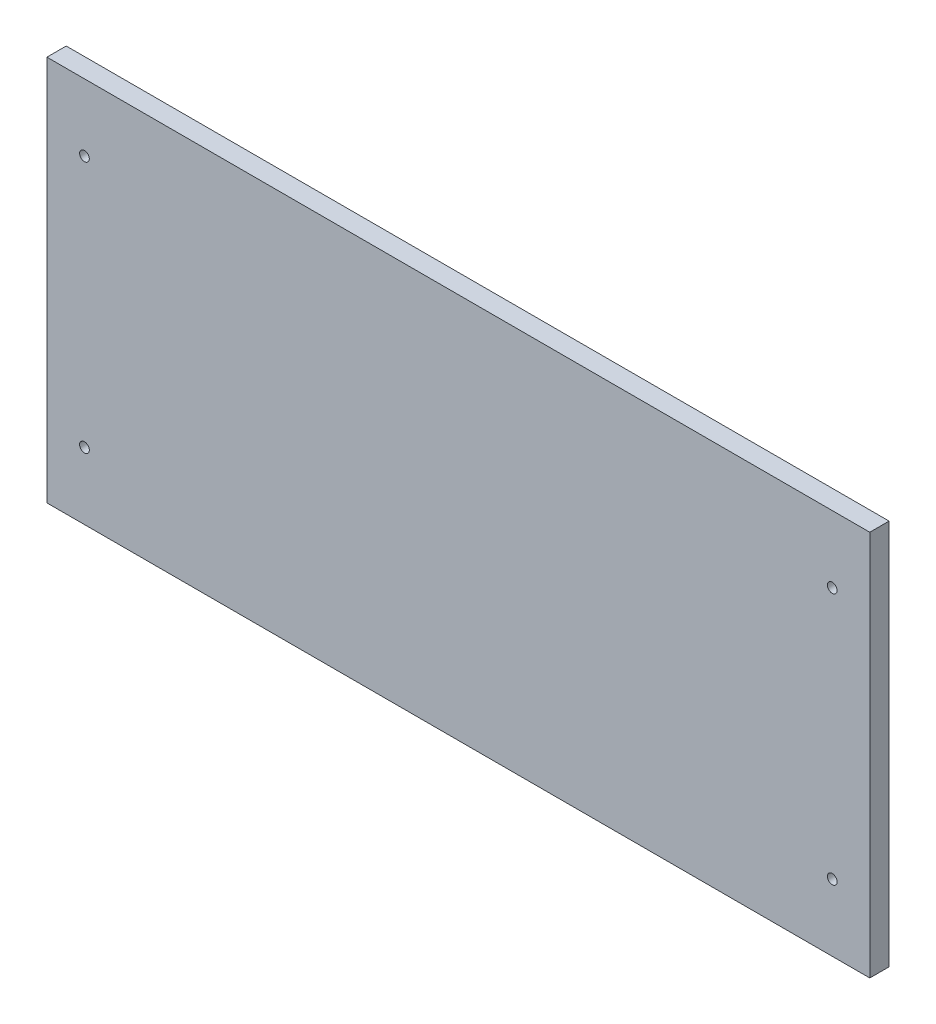
SolidWorks part; units mm, degrees
ref_plane "Front Plane" through (0, 0, 0) normal (0, 0, 1) x (1, 0, 0)
ref_plane "Top Plane" through (0, 0, 0) normal (0, 1, 0) x (1, 0, 0)
ref_plane "Right Plane" through (0, 0, 0) normal (1, 0, 0) x (0, 0, -1)
sketch "Sketch1" plane through (0, 0, 0) normal (0, 0, 1) x (1, 0, 0)
  line L0 (135.35, 127) -> (135.35, 0) construction
  line L1 (0, 0) -> (270.7, 0)
  line L2 (0, 0) -> (0, 127)
  line L3 (0, 127) -> (270.7, 127)
  line L4 (270.7, 0) -> (270.7, 127)
  line L5 (0, 63.5) -> (270.7, 63.5) construction
  circle A3 centre (12.35, 105) radius 1.6
  circle A7 centre (258.35, 105) radius 1.6
  circle A8 centre (258.35, 22) radius 1.6
  circle A9 centre (12.35, 22) radius 1.6
  dimension "D11" = 3.2
  dimension "D1" = 127
  dimension "D2" = 270.7
  dimension "D12" = 12.35
  dimension "D13" = 22
extrude "Wall" add sketch "Sketch1" along normal blind 6.35
sketch "Sketch2" plane through (0, 0, 6.35) normal (0, 0, 1) x (1, 0, 0)
  line L0 (135.35, 127) -> (135.35, 98.425) construction
  line L1 (270.7, 127) -> (0, 127) construction
  line L2 (135.35, 98.425) -> (66.6667, 98.425) construction
  line L3 (135.35, 98.425) -> (204.0333, 98.425) construction
  line L4 (0, 127) -> (0, 0) construction
  circle A0 centre (135.35, 98.425) radius 3.9687
  circle A1 centre (66.6667, 98.425) radius 3.9688
  circle A2 centre (204.0333, 98.425) radius 3.9687
  dimension "D2" = 7.9375
  dimension "D1" = 28.575
  dimension "D3" = 66.6667
extrude "RodSupportCutouts" [suppressed] cut sketch "Sketch2" against normal up to next
sketch "Sketch3" plane through (0, 0, 6.35) normal (0, 0, 1) x (1, 0, 0)
  line L1 (25.4, 88.9) -> (245.3, 88.9)
  line L2 (25.4, 88.9) -> (25.4, 114.3)
  line L3 (25.4, 114.3) -> (245.3, 114.3)
  line L4 (245.3, 88.9) -> (245.3, 114.3)
  line L5 (25.4, 88.9) -> (245.3, 114.3) construction
  line L6 (25.4, 114.3) -> (245.3, 88.9) construction
  line L7 (270.7, 127) -> (0, 127) construction
  line L8 (0, 127) -> (0, 0) construction
  point P0 (135.35, 101.6)
  point P9 (135.35, 127)
  dimension "D1" = 25.4
  dimension "D2" = 25.4
  dimension "D3" = 25.4
extrude "CannulaLargeCutout" [suppressed] cut sketch "Sketch3" against normal up to next
sketch "Sketch4" [suppressed] plane through (0, 0, 9.525) normal (0, 0, 1) x (1, 0, 0)
  line L0 (6, 103.5) -> (194, 103.5) construction
  line L1 (6, 105) -> (6, 22) construction
  line L2 (194, 105) -> (194, 22) construction
  line L3 (200, 127) -> (0, 127) construction
  line L4 (0, 127) -> (0, 0) construction
  circle A0 centre (60, 103.5) radius 6.35
  circle A1 centre (20, 103.5) radius 6.35
  circle A2 centre (100, 103.5) radius 6.35
  circle A3 centre (140, 103.5) radius 6.35
  circle A4 centre (60, 63.5) radius 6.35
  circle A5 centre (100, 63.5) radius 6.35
  circle A6 centre (140, 63.5) radius 6.35
  circle A7 centre (60, 23.5) radius 6.35
  circle A8 centre (100, 23.5) radius 6.35
  circle A9 centre (140, 23.5) radius 6.35
  circle A10 centre (20, 63.5) radius 6.35
  circle A11 centre (20, 23.5) radius 6.35
  circle A12 centre (180, 103.5) radius 6.35
  circle A13 centre (180, 63.5) radius 6.35
  circle A14 centre (180, 23.5) radius 6.35
  point P42 (100, 127)
  point P45 (0, 63.5)
  dimension "D3" = 12.7
  dimension "D1" = 5
  dimension "D2" = 3
extrude "CannulaHoles" [suppressed] cut sketch "Sketch4" against normal up to next
ref_plane "LeftBoundary" through (25.4, 0, 0) normal (-1, 0, 0) x (0, 0, 1)
ref_plane "RightBoundary" through (245.3, 0, 0) normal (1, 0, 0) x (0, 0, -1)
ref_plane "TopBoundary" through (0, 101.6, 0) normal (0, 1, 0) x (1, 0, 0)
ref_plane "BottomBoundary" through (0, 25.4, 0) normal (0, -1, 0) x (-1, 0, 0)
sketch "Sketch5" plane through (0, 0, 6.35) normal (0, 0, 1) x (1, 0, 0)
  line L4 (25.4, 3.4925) -> (25.4, -3.4925) construction
  line L5 (3.4925, 101.6) -> (-3.4925, 101.6) construction
  circle A0 centre (25.4, 101.6) radius 3.9687
  dimension "D1" = 7.9375
extrude "RodSupportCutout" [suppressed] cut sketch "Sketch5" against normal up to next
pattern_linear "SupportPattern" [suppressed] count 7 spacing 36.65 count 5 spacing 19.05 of bodies 105
equation "\"Length\"= 283mm"
equation "\"Width\"= 225mm"
equation "\"WallThickness\"= 0.25in"
equation "\"UpperWaterJacketThickness\"= 28mm"
equation "\"SpacerHeight\"= 80.2mm"
equation "\"SpacerCornerWidth\"= 10mm"
equation "\"SpacerCornerHeight\"= 60.16mm"
equation "\"SpacerPegDiameter\"= 10mm"
equation "\"SpacerPegHeight\"= 10mm"
equation "\"TubingShort\"= 110mm"
equation "\"TubingLong\"= 175mm"
equation "\"PlateLength\"= 252mm"
equation "\"PlateWidth\"= 190mm"
equation "\"PlateHoleDiameter\"= 5.9mm"
equation "\"PlateHoleBottom\"= 2mm"
equation "\"PlateHoleSide\"= 1.55mm"
equation "\"PlateHoleSpacing\"= 3.1mm"
equation "\"PlateThickness\"= 1.55mm"
equation "\"ReservoirBottom\"= 12.5mm"
equation "\"ReservoirSupportWidth\"= 12mm"
equation "\"ReservoirSupportHeight\"= 15.1mm"
equation "\"ReservoirSupportPlacementHeight\"= 50mm"
equation "\"ReservoirHoleDiameter\"= 12.7mm"
equation "\"ReservoirHoleRight\"= 25mm"
equation "\"ReservoirHoleTop\"= \"ReservoirSupportPlacementHeight\""
equation "\"ReservoirHeight\"= 90mm"
equation "\"ReservoirPortBottom\"= 4mm"
equation "\"ReservoirPortTop\"= 10mm"
equation "\"ReservoirPortWidth\"= 101mm"
equation "\"CustomSpacerHeight\"= 5in"
equation "\"CustomSpacerRodHoleHeight\"= .75in"
equation "\"CustomSpacerRodHoleDiameter\"= .3125in"
equation "\"ScrewBlockSide\"= 12mm"
equation "\"ScrewBlockUpperHeight\"= 16mm"
equation "\"ScrewBlockLowerHeight\"= 16mm"
equation "\"InternalLength\"= 258mm"
equation "\"InternalWidth\"= 200mm"
equation "\"CustomSpacerPegHeight\"= 1in"
equation "\"CustomSpacerScrewBore\"=3.2mm"
equation "\"CustomSpacerScrewDepth\"=10mm"
equation "\"D1@Sketch1\"=\"CustomSpacerHeight\""
equation "\"D2@Sketch1\"=\"WallLength\""
equation "\"D11@Sketch1\"=\"CustomSpacerScrewBore\""
equation "\"D12@Sketch1\"  = \"ScrewBlockSide\"/2 + \"WallThickness\""
equation "\"D13@Sketch1\"=\"ScrewBlockUpperHeight\"+\"ScrewBlockSide\"/2"
equation "\"D1@Wall\" = \"WallThickness\""
equation "\"D1@Sketch2\"=\"CustomSpacerRodHoleHeight\" + \"CustomSpacerRodHoleDiameter\" +0.0625in"
equation "\"D2@Sketch2\"=\"CustomSpacerRodHoleDiameter\""
equation "\"D3@Sketch2\"=\"InternalWidth\" / 3"
equation "\"D1@Sketch3\"=1in"
equation "\"WallLength\"= \"InternalLength\" + ( 2 * \"WallThickness\" )"
equation "\"D1@Sketch5\"=\"CustomSpacerRodHoleDiameter\""
